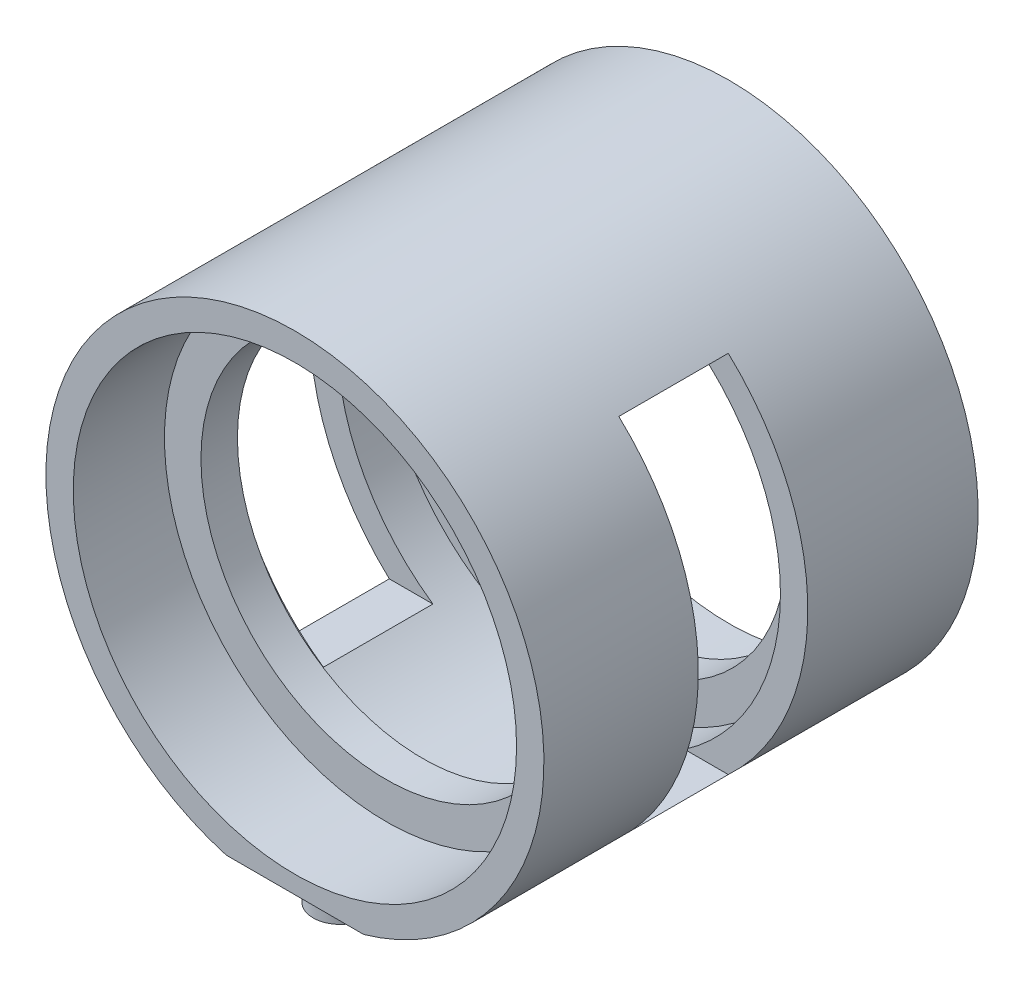
SolidWorks part; units mm, degrees
ref_plane "Front Plane" through (0, 0, 0) normal (0, 0, 1) x (1, 0, 0)
ref_plane "Top Plane" through (0, 0, 0) normal (0, 1, 0) x (1, 0, 0)
ref_plane "Right Plane" through (0, 0, 0) normal (1, 0, 0) x (0, 0, -1)
sketch "Sketch1" plane through (0, 0, 0) normal (0, 0, 1) x (1, 0, 0)
  line L0 (-3.7667, -13.12) -> (3.7667, -13.12)
  line L1 (0, -55) -> (0, 55) construction
  line L2 (0, -13.65) -> (6.7961, -13.65) construction
  circle A0 centre (0, 0) radius 12.15
  circle A1 centre (0, 0) radius 13.65
  point P6 (0, -13.12)
  point P11 (0, 0)
  point P12 (0, -13.65)
  dimension "D1" = 24.3
  dimension "D2" = 27.3
  dimension "D3" = 0.53
extrude "Boss-Extrude1" add sketch "Sketch1" along normal blind 23.8 contours L0 A1 A0 region at (-7.983, 10.5973, 0)
sketch "Sketch2" plane through (0, 0, 23.8) normal (0, 0, 1) x (1, 0, 0)
  circle A1 centre (0, 0) radius 12.15
  circle A2 centre (0, 0) radius 10.15
  circle A3 centre (0, 0) radius 10.15
  dimension "D1" = 2
extrude "Boss-Extrude2" add sketch "Sketch2" against normal blind 2 from offset 5 offset against normal yes
extrude "Boss-Extrude3" add sketch "Sketch2<2>" along normal blind 2 from offset 18.8 offset against normal yes
sketch "Sketch2<2>" plane through (0, 0, 23.8) normal (0, 0, 1) x (1, 0, 0) same geometry as "Sketch2"
sketch "Sketch4" plane through (0, 0, 0) normal (1, 0, 0) x (0, 0, -1)
  line L0 (13.09, 0) -> (-13.09, 0) construction
  line L1 (-15.3358, -10) -> (-9.3358, -10)
  line L2 (-15.3358, -10) -> (-15.3358, 10)
  line L3 (-15.3358, 10) -> (-9.3358, 10)
  line L4 (-9.3358, -10) -> (-9.3358, 10)
  line L5 (-15.3358, -10) -> (-9.3358, 10) construction
  line L6 (-15.3358, 10) -> (-9.3358, -10) construction
  point P0 (-12.3358, 0)
  dimension "D1" = 20
  dimension "D2" = 6
extrude "Cut-Extrude1" cut sketch "Sketch4" against normal through all both and the other way through all
sketch "Sketch5" plane through (0, -13.12, 0) normal (0, -1, 0) x (1, 0, 0)
  line L0 (0, 23.8) -> (0, 0) construction
  line L1 (-3.7667, 23.8) -> (3.7667, 23.8) construction
  line L2 (0, 21.3) -> (0, 2.5) construction
  circle A0 centre (0, 21.3) radius 1.5
  circle A1 centre (0, 2.5) radius 1.5
  point P7 (0, 11.9)
  point P8 (0, 11.9)
  dimension "D2" = 3
  dimension "D3" = 3
  dimension "D1" = 18.8
extrude "Boss-Extrude4" add sketch "Sketch5" along normal blind 1.6
